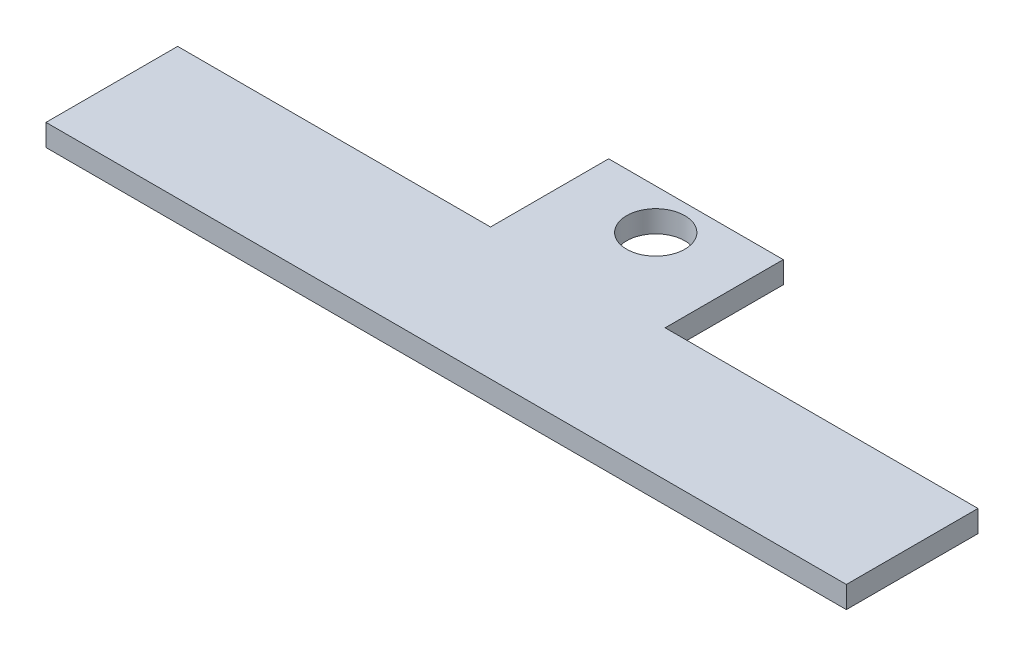
SolidWorks part; units mm, degrees
ref_plane "Спереди" through (0, 0, 0) normal (0, 0, 1) x (1, 0, 0)
ref_plane "Сверху" through (0, 0, 0) normal (0, 1, 0) x (1, 0, 0)
ref_plane "Справа" through (0, 0, 0) normal (1, 0, 0) x (0, 0, -1)
sketch "Эскиз1" plane through (0, 0, 0) normal (0, 1, 0) x (1, 0, 0)
  line L0 (0, 9.0465) -> (21.5, 9.0465)
  line L1 (0, 0) -> (55, 0)
  line L2 (0, 0) -> (0, 9.0465)
  line L4 (55, 0) -> (55, 9.0465)
  line L5 (21.5, 9.0465) -> (21.5, 17.1649)
  line L6 (21.5, 17.1649) -> (33.5, 17.1649)
  line L7 (33.5, 17.1649) -> (33.5, 9.0465)
  line L8 (33.5, 9.0465) -> (55, 9.0465)
  line L9 (27.5, 0) -> (27.5, 34.3298) construction
  circle A2 centre (27.5, 14.4) radius 2
  point P11 (0, 0)
  point P12 (0, 0)
  point P13 (27.5, 17.1649)
extrude "Бобышка-Вытянуть1" add sketch "Эскиз1" along normal blind 1.5
